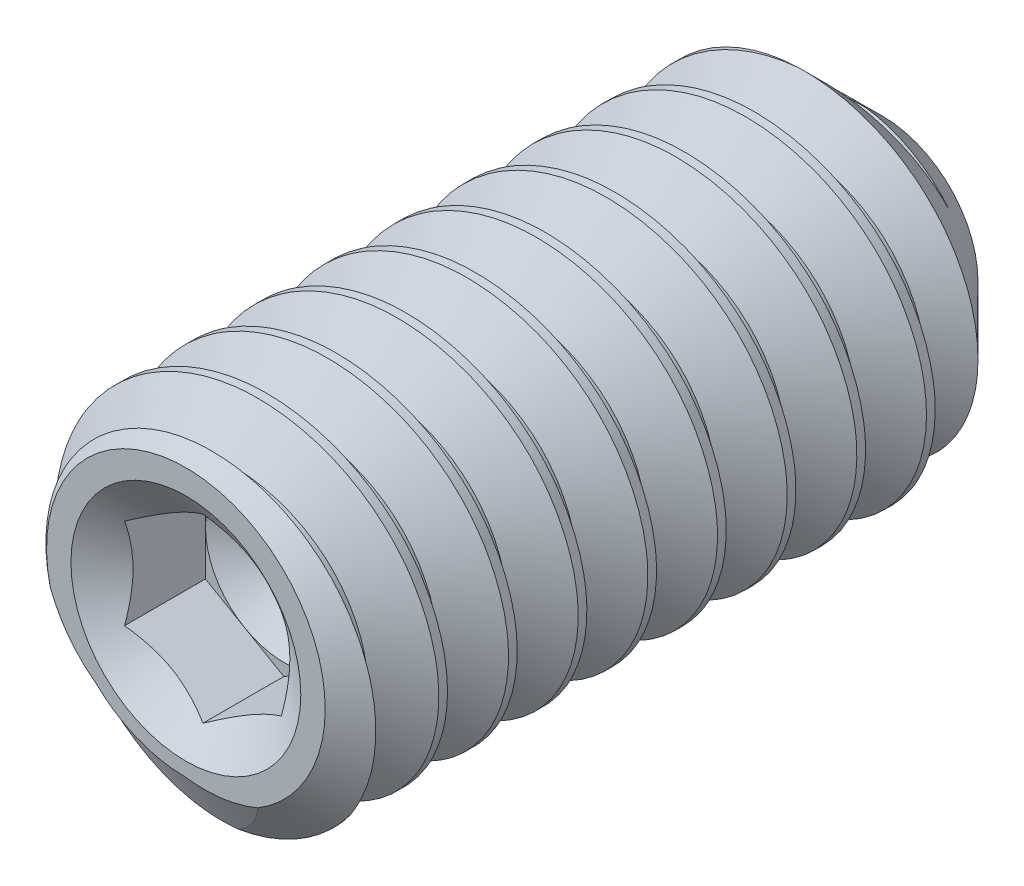
SolidWorks part; units mm, degrees
ref_plane "Front" through (0, 0, 0) normal (0, 0, 1) x (1, 0, 0)
ref_plane "Top" through (0, 0, 0) normal (0, 1, 0) x (1, 0, 0)
ref_plane "Right" through (0, 0, 0) normal (1, 0, 0) x (0, 0, -1)
sketch "Sketch1" plane through (0, 0, 0) normal (1, 0, 0) x (0, 0, -1)
  line L0 (-1.8354, 0) -> (-1.8354, 0.8)
  line L1 (-1.8354, 0.8) -> (-1.6953, 1)
  line L2 (-1.6953, 1) -> (1.7126, 1)
  line L3 (1.7126, 1) -> (2.1646, 0.548)
  line L4 (2.1646, 0.548) -> (1.8354, 0)
  line L5 (1.8354, 0) -> (-1.8354, 0)
  line L6 (1.8354, 0) -> (2.1646, 0) construction
  line L7 (2.1646, 0) -> (2.1646, 0.548) construction
  line L8 (2.1646, -0.548) -> (1.8354, 0) construction
  line L9 (-1.6953, -1) -> (1.7126, -1) construction
  line L10 (0, 0) -> (0, -0.4) construction
  point P11 (-1.8354, 1)
  point P12 (-3.5374, -1)
  point P14 (2.1646, 1)
  dimension "Dia" = 2
  dimension "Length" = 4
  dimension "D3" = 35
  dimension "D5" = 118
  dimension "D6" = 45
  dimension "D7" = 1.6
  dimension "Pitch" = 0.4
  dimension "D1" = 5.25
revolve "Revolve1" add sketch "Sketch1" angle 360 about L6
sketch "Sketch2" plane through (0, 0, 1.8354) normal (0, 0, 1) x (1, 0, 0)
  line L1 (0, 0.5196) -> (-0.45, 0.2598)
  line L2 (-0.45, 0.2598) -> (-0.45, -0.2598)
  line L3 (-0.45, -0.2598) -> (0, -0.5196)
  line L4 (0, -0.5196) -> (0.45, -0.2598)
  line L5 (0.45, -0.2598) -> (0.45, 0.2598)
  line L6 (0.45, 0.2598) -> (0, 0.5196)
  circle A0 centre (0, 0) radius 0.45 construction
  circle A1 centre (0, 0) radius 1 construction
  dimension "Hex" = 0.9
extrude "Cut-Extrude1" cut sketch "Sketch2" against normal blind 0.5625
sketch "Sketch3" plane through (0, 0, 1.8354) normal (0, 0, 1) x (1, 0, 0)
  line L0 (0, 0.5196) -> (0, 0.8) construction
  circle A0 centre (0, 0) radius 0.6598
  point P5 (0, 0.6598)
  dimension "D1" = 0.1402
extrude "Cut-Extrude2" cut sketch "Sketch3" against normal through all draft 55
sketch "Sketch4" plane through (0, 0, 1.2729) normal (0, 0, 1) x (1, 0, 0)
  circle A0 centre (0, 0) radius 0.45 construction
  circle A1 centre (0, 0) radius 0.45
extrude "Cut-Extrude3" cut sketch "Sketch4" against normal through all draft 60
ref_plane "Plane1" through (0, 0, -2.1646) normal (0, 0, 1) x (1, 0, 0)
sketch "Sketch5" plane through (0, 0, -2.1646) normal (0, 0, 1) x (1, 0, 0)
  circle A0 centre (0, 0) radius 1 construction
  circle A1 centre (0, 0) radius 1
curve "Helix/Spiral1" pitch 0.4 height 4.4 radius 1 centre (0, 0, -2.1646) axis (0, 0, 1) start towards (0, 1, 0)
sketch "Sketch6" plane through (0, 0, 0) normal (1, 0, 0) x (0, 0, -1)
  line L0 (2.1396, 1.0433) -> (2.5396, 1.0433) construction
  line L1 (2.5396, 1.0433) -> (2.3396, 0.6969) construction
  line L2 (2.3396, 0.6969) -> (2.1396, 1.0433) construction
  line L3 (2.1646, 1) -> (2.5146, 1) construction
  line L4 (2.3146, 0.7402) -> (2.3646, 0.7402) construction
  line L5 (2.3396, 1) -> (2.3396, 1.0433) construction
  line L7 (2.3396, 0.7402) -> (2.3396, 0.6969) construction
  line L8 (2.3396, 1.0217) -> (2.1521, 1.0217) construction
  line L9 (2.3146, 0.7402) -> (2.1521, 1.0217)
  line L10 (2.1521, 1.0217) -> (2.5271, 1.0217)
  line L11 (2.5271, 1.0217) -> (2.3646, 0.7402)
  line L12 (2.3646, 0.7402) -> (2.3146, 0.7402)
  dimension "D1" = 0.4
  dimension "D2" = 0.05
sweep "Cut-Sweep1" cut profiles "Sketch6" path "Helix/Spiral1"
ref_axis "Center Axis 1" through (0, 0, 3.3456) along (0, 0, -1)
ref_plane "Contact Plane 1" through (0, 0, 1.8354) normal (0, 0, 1) x (1, 0, 0)
ref_plane "Contact Plane 2" through (0, 0, -2.1646) normal (0, 0, 1) x (1, 0, 0)
equation "\"D7@Sketch1\" = \"Dia@Sketch1\" * .8"
equation "\"hex Depth@Cut-Extrude1\" = \"Hex@Sketch2\" * .625"
equation "\"D3@Helix/Spiral1\" = \"Length@Sketch1\" + \"Pitch@Sketch1\""
equation "\"D4@Helix/Spiral1\" = \"Pitch@Sketch1\""
equation "\"D1@Sketch6\" = \"Pitch@Sketch1\""
equation "\"D2@Sketch6\"=\"D1@Sketch6\"/8"
